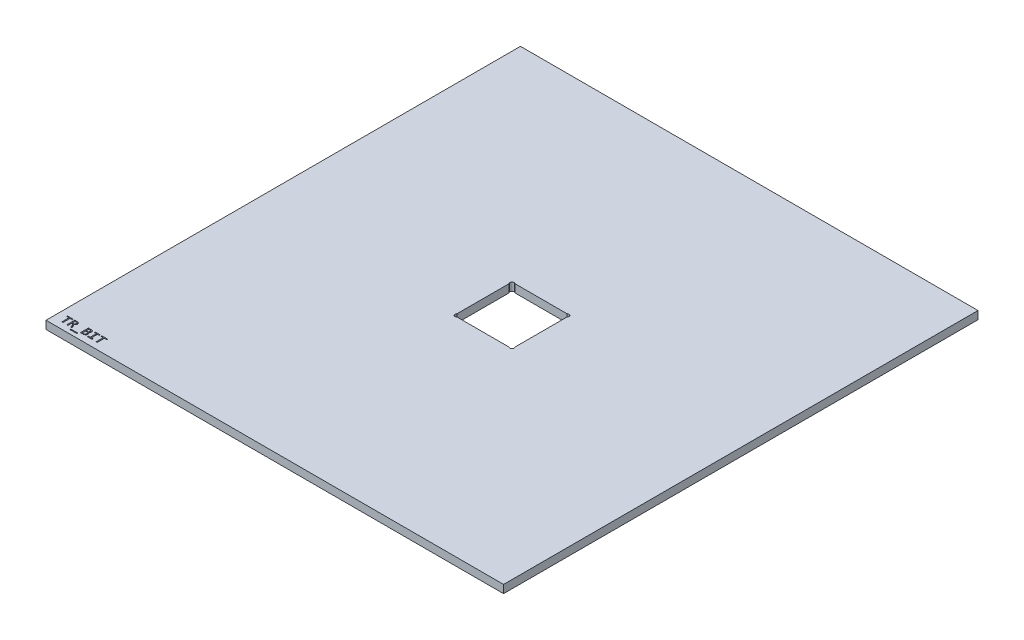
SolidWorks part; units mm, degrees
ref_plane "Front" through (0, 0, 0) normal (0, 0, 1) x (1, 0, 0)
ref_plane "Top" through (0, 0, 0) normal (0, 1, 0) x (1, 0, 0)
ref_plane "Right" through (0, 0, 0) normal (1, 0, 0) x (0, 0, -1)
sketch "Sketch1" plane through (0, 0, 0) normal (0, 1, 0) x (1, 0, 0)
  line L1 (-90.424, -93.7578) -> (90.424, -93.7578)
  line L2 (-90.424, -93.7578) -> (-90.424, 93.7578)
  line L3 (-90.424, 93.7578) -> (90.424, 93.7578)
  line L4 (90.424, -93.7578) -> (90.424, 93.7578)
  line L5 (-90.424, -93.7578) -> (90.424, 93.7578) construction
  line L6 (-90.424, 93.7578) -> (90.424, -93.7578) construction
  point P0 (0, 0)
  dimension "D1" = 180.848
  dimension "D2" = 187.5155
extrude "Boss-Extrude1" add sketch "Sketch1" along normal blind 3.175
sketch "Sketch2" plane through (0, 3.175, 0) normal (0, 1, 0) x (1, 0, 0)
  line L0 (-90.424, 93.7578) -> (90.424, -93.7578) construction
  line L2 (-11.43, -11.43) -> (11.43, -11.43)
  line L3 (-11.43, -11.43) -> (-11.43, 11.43)
  line L4 (-11.43, 11.43) -> (11.43, 11.43)
  line L5 (11.43, -11.43) -> (11.43, 11.43)
  line L6 (-11.43, -11.43) -> (11.43, 11.43) construction
  line L7 (-11.43, 11.43) -> (11.43, -11.43) construction
  point P4 (0, 0)
  dimension "D1" = 22.86
extrude "Cut-Extrude1" cut sketch "Sketch2" against normal blind 3.175
sketch "Sketch3" plane through (0, 3.175, 0) normal (0, 1, 0) x (1, 0, 0)
  line L0 (-11.43, 11.43) -> (-10.3075, 11.43) construction
  line L1 (11.43, 11.43) -> (-11.43, 11.43) construction
  line L2 (-11.43, 11.43) -> (-11.43, 10.3075) construction
  line L3 (11.43, 11.43) -> (11.43, 10.3075) construction
  line L4 (11.43, 11.43) -> (10.3075, 11.43) construction
  line L5 (11.43, -11.43) -> (10.3075, -11.43) construction
  line L6 (11.43, -11.43) -> (11.43, -10.3075) construction
  line L7 (-11.43, -11.43) -> (-11.43, -10.3075) construction
  line L8 (-11.43, -11.43) -> (-10.3075, -11.43) construction
  circle A0 centre (-10.8687, 10.8687) radius 0.7937
  circle A1 centre (10.8687, 10.8687) radius 0.7938
  circle A2 centre (10.8687, -10.8687) radius 0.7938
  circle A3 centre (-10.8687, -10.8687) radius 0.7938
  point P8 (0, 0)
  point P28 (0, 0)
  dimension "D1" = 1.5875
  dimension "D2" = 4
extrude "Cut-Extrude2" cut sketch "Sketch3" against normal through all
sketch "Sketch4" plane through (0, 3.175, 0) normal (0, 1, 0) x (1, 0, 0)
  line L0 (-87.884, -91.2177) -> (90.424, -91.2177) construction
  line L1 (-90.424, -93.7578) -> (-87.884, -93.7578) construction
  line L2 (-90.424, -93.7578) -> (-90.424, -91.2177) construction
  line L3 (-90.424, -91.2177) -> (-87.884, -91.2177) construction
  line L4 (-87.884, -93.7578) -> (-87.884, -91.2177) construction
  line L5 (90.424, -93.7578) -> (90.424, 93.7578) construction
  text T0 "TR_BIT" font "Consolas" height 3.175
  dimension "D1" = 2.54
extrude "Cut-Extrude3" cut sketch "Sketch4" against normal blind 1.5875
